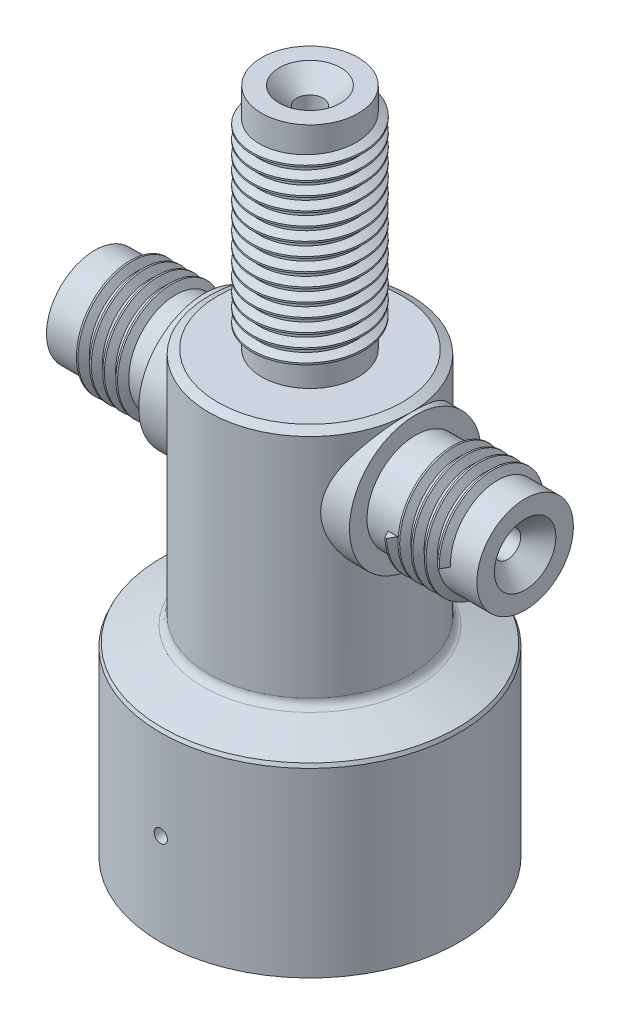
SolidWorks part; units mm, degrees
material "Литая легированная сталь"
ref_plane "Спереди" through (0, 0, 0) normal (0, 0, 1) x (1, 0, 0)
ref_plane "Сверху" through (0, 0, 0) normal (0, 1, 0) x (1, 0, 0)
ref_plane "Справа" through (0, 0, 0) normal (1, 0, 0) x (0, 0, -1)
sketch "Эскиз2" plane through (0, 0, 0) normal (0, 0, 1) x (1, 0, 0)
  line L0 (0, 0) -> (-17, 0)
  line L1 (-17, 0) -> (-17, 21)
  line L2 (-17, 21) -> (-11.5, 23.0018)
  line L3 (-11.5, 23.0018) -> (-11.5, 50)
  line L4 (-11.5, 50) -> (-5.5, 50)
  line L5 (-5.5, 50) -> (-5.5, 76)
  line L6 (-5.5, 76) -> (0, 76)
  line L7 (0, 76) -> (0, 0)
  dimension "D1" = 76
  dimension "D2" = 17
  dimension "D3" = 5.5
  dimension "D4" = 11.5
  dimension "D5" = 21
  dimension "D6" = 26
  dimension "D7" = 70
revolve "Повернуть2" add sketch "Эскиз2" angle 360 about L7
chamfer "Фаска1" distance 0.2 angle 45 1 edges at (0, 21, 17)
fillet "Скругление2" radius 1 1 edges at (0, 23.0018, 11.5)
sketch "Эскиз7" plane through (0, 0, 0) normal (1, 0, 0) x (0, 0, -1)
  line L0 (0, 0) -> (0, 50) construction
  circle A0 centre (0, 42) radius 5.5
  point P3 (0, 42)
  dimension "D3" = 11
  dimension "D1" = 50
  dimension "D2" = 8
extrude "Бобышка-Вытянуть3" add sketch "Эскиз7" along normal blind 24.5
sketch "Эскиз8" plane through (0, 0, 0) normal (1, 0, 0) x (0, 0, -1)
  line L0 (0, 0) -> (0, 42) construction
  circle A0 centre (0, 42) radius 5.5
  dimension "D2" = 11
  dimension "D1" = 42
extrude "Бобышка-Вытянуть4" add sketch "Эскиз8" against normal blind 24.5
sketch "Эскиз9" plane through (0, 0, 0) normal (1, 0, 0) x (0, 0, -1)
  circle A0 centre (0, 42) radius 7.5
  point P0 (0, 42)
  dimension "D2" = 15
  dimension "D1" = 42
extrude "Бобышка-Вытянуть5" add sketch "Эскиз9" along normal blind 12 contours A0
sketch "Эскиз10" plane through (0, 0, 0) normal (1, 0, 0) x (0, 0, -1)
  circle A0 centre (0, 42) radius 7.5
  point P0 (0, 42)
  dimension "D2" = 15
  dimension "D1" = 42
extrude "Бобышка-Вытянуть6" add sketch "Эскиз10" against normal blind 12 contours A0
thread "Резьба1" pitch 1.5 start angle 0, offset 3, length 0, pitch 1.5, diameter 11
ref_plane "Плоскость3" through (21.5, 42, 5.5) normal (0, -1, 0) x (0, 0, 1)
sketch "Профиль резьбы2" plane through (21.5, 42, 5.5) normal (0, -1, 0) x (0, 0, 1)
  line L0 (0, 0) -> (0, 1.5) construction
  line L1 (0, 0) -> (0.8119, 0.4687)
  line L2 (0.8119, 0.4687) -> (0.8119, 0.6562)
  line L3 (0.8119, 0.6562) -> (0, 1.125)
  line L4 (0.8119, 0.5625) -> (0, 0.5625) construction
  line L11 (0, 0) -> (0, 1.125)
  point P2 (0, 0)
  dimension "Pitch" = 1.5
  dimension "Profile_Angle" = 60
  dimension "Profile_Land" = 0.1875
  dimension "Profile_Height" = 0.8119
thread "Резьба2" pitch 1.5 profile "Профиль резьбы3" start angle 0, offset 3, length 0, pitch 1.5, diameter 11
ref_plane "Плоскость4" through (-21.5, 42, -5.5) normal (0, -1, 0) x (0, 0, -1)
sketch "Профиль резьбы3" plane through (-21.5, 42, -5.5) normal (0, -1, 0) x (0, 0, -1)
  line L0 (0, 0) -> (0, 1.5) construction
  line L1 (0, 0) -> (0.8119, 0.4687)
  line L2 (0.8119, 0.4687) -> (0.8119, 0.6562)
  line L3 (0.8119, 0.6562) -> (0, 1.125)
  line L4 (0.8119, 0.5625) -> (0, 0.5625) construction
  line L11 (0, 0) -> (0, 1.125)
  point P2 (0, 0)
  dimension "Pitch" = 1.5
  dimension "Profile_Angle" = 60
  dimension "Profile_Land" = 0.1875
  dimension "Profile_Height" = 0.8119
thread "Резьба3" pitch 1.5 profile "Профиль резьбы4" start angle 0, offset 2, length 0, pitch 1.5, diameter 11
ref_plane "Плоскость5" through (-5.5, 74, 0) normal (0, 0, 1) x (-1, 0, 0)
sketch "Профиль резьбы4" plane through (-5.5, 74, 0) normal (0, 0, 1) x (-1, 0, 0)
  line L0 (0, 0) -> (0, 1.5) construction
  line L1 (0, 0) -> (0.8119, 0.4687)
  line L2 (0.8119, 0.4687) -> (0.8119, 0.6562)
  line L3 (0.8119, 0.6562) -> (0, 1.125)
  line L4 (0.8119, 0.5625) -> (0, 0.5625) construction
  line L11 (0, 0) -> (0, 1.125)
  point P2 (0, 0)
  dimension "Pitch" = 1.5
  dimension "Profile_Angle" = 60
  dimension "Profile_Land" = 0.1875
  dimension "Profile_Height" = 0.8119
ref_plane "Плоскость6" through (24.5, 0, 0) normal (1, 0, 0) x (0, 0, -1)
sketch "Эскиз24" plane through (24.5, 0, 0) normal (1, 0, 0) x (0, 0, -1)
  line L0 (-5.5, 42) -> (5.5, 42) construction
  circle A0 centre (0, 42) radius 5.5 construction
  circle A1 centre (0, 42) radius 1.5
  dimension "D1" = 3
extrude "Вырез-Вытянуть1" cut sketch "Эскиз24" against normal blind 10 contours A1
chamfer "Фаска2" distance 2 angle 45 1 edges at (24.5, 42, -1.5)
ref_plane "Плоскость7" through (0, 76, 0) normal (0, 1, 0) x (1, 0, 0)
sketch "Эскиз25" plane through (0, 76, 0) normal (0, 1, 0) x (1, 0, 0)
  line L0 (0, -5.5) -> (0, 5.5) construction
  circle A0 centre (0, 0) radius 5.5 construction
  circle A1 centre (0, 0) radius 1.5
  dimension "D1" = 3
extrude "Вырез-Вытянуть2" cut sketch "Эскиз25" against normal through all
chamfer "Фаска3" distance 2 angle 45 1 edges at (0, 76, 1.5)
ref_plane "Плоскость8" through (-24.5, 0, 0) normal (-1, 0, 0) x (0, 0, 1)
sketch "Эскиз26" plane through (-24.5, 0, 0) normal (-1, 0, 0) x (0, 0, 1)
  line L0 (-5.5, 42) -> (5.5, 42) construction
  circle A0 centre (0, 42) radius 5.5 construction
  circle A1 centre (0, 42) radius 1.5
  dimension "D1" = 3
extrude "Вырез-Вытянуть3" cut sketch "Эскиз26" against normal blind 10
chamfer "Фаска4" distance 2 angle 45 1 edges at (-24.5, 42, 1.5)
ref_plane "Плоскость9" through (0, 0, 0) normal (0, -1, 0) x (-1, 0, 0)
sketch "Эскиз27" plane through (0, 0, 0) normal (0, -1, 0) x (-1, 0, 0)
  circle A0 centre (0, 0) radius 13
  dimension "D1" = 26
extrude "Вырез-Вытянуть4" cut sketch "Эскиз27" against normal blind 16 contours A0
chamfer "Фаска5" distance 0.8 angle 30 1 edges at (0, 0, -13)
thread "Резьба4" pitch 1.5 profile "Профиль резьбы6" start angle 0, offset 3, length 0, pitch 1.5, diameter 26
ref_plane "Плоскость11" through (-13, 13, 0) normal (0, 0, 1) x (-1, 0, 0)
sketch "Профиль резьбы6" plane through (-13, 13, 0) normal (0, 0, 1) x (-1, 0, 0)
  line L0 (0, 0) -> (0, 1.5) construction
  line L1 (0, 0) -> (0.8119, 0.4687)
  line L2 (0.8119, 0.4687) -> (0.8119, 0.6562)
  line L3 (0.8119, 0.6562) -> (0, 1.125)
  line L4 (0.8119, 0.5625) -> (0, 0.5625) construction
  line L11 (0, 0) -> (0, 1.125)
  point P2 (0, 0)
  dimension "Pitch" = 1.5
  dimension "Profile_Angle" = 60
  dimension "Profile_Land" = 0.1875
  dimension "Profile_Height" = 0.8119
ref_plane "Плоскость12" through (0, 16, 0) normal (0, -1, 0) x (-1, 0, 0)
sketch "Эскиз32" plane through (0, 16, 0) normal (0, -1, 0) x (-1, 0, 0)
  circle A0 centre (0, 0) radius 9
  dimension "D1" = 18
extrude "Вырез-Вытянуть5" cut sketch "Эскиз32" against normal blind 20 contours A0
sketch "Эскиз33" plane through (0, 16, 0) normal (0, -1, 0) x (-1, 0, 0)
  circle A0 centre (0, 0) radius 10
  circle A1 centre (0, 0) radius 11.5
  dimension "D1" = 20
  dimension "D2" = 23
extrude "Бобышка-Вытянуть8" add sketch "Эскиз33" along normal blind 1
fillet "Скругление3" radius 0.4 1 edges at (0, 15, -11.5)
chamfer "Фаска6" distance 1 angle 30 1 edges at (0, 16, -9)
sketch "Эскиз34" plane through (0, 36, 0) normal (0, -1, 0) x (1, 0, 0)
  circle A0 centre (0, 0) radius 5
  dimension "D1" = 10
extrude "Вырез-Вытянуть7" cut sketch "Эскиз34" against normal blind 6
sketch "Эскиз35" plane through (0, 42, 0) normal (0, -1, 0) x (1, 0, 0)
  circle A0 centre (0, 0) radius 3
  circle A1 centre (0, 0) radius 1.5
  dimension "D1" = 6
  dimension "D2" = 3
extrude "Бобышка-Вытянуть9" add sketch "Эскиз35" along normal blind 1
fillet "Скругление5" radius 1 1 edges at (0, 41, -3)
ref_plane "Плоскость13" through (0, 0, 17) normal (0, 0, 1) x (1, 0, 0)
sketch "Эскиз36" plane through (0, 0, 17) normal (0, 0, 1) x (1, 0, 0)
  line L0 (0, 0) -> (0, 21) construction
  circle A0 centre (0, 10.5) radius 0.75
  dimension "D1" = 1.5
  dimension "D2" = 21
extrude "Вырез-Вытянуть8" cut sketch "Эскиз36" against normal blind 11 contours A0
chamfer "Фаска7" distance 0.5 distance2 1 1 edges at (0, 50, 11.5)
